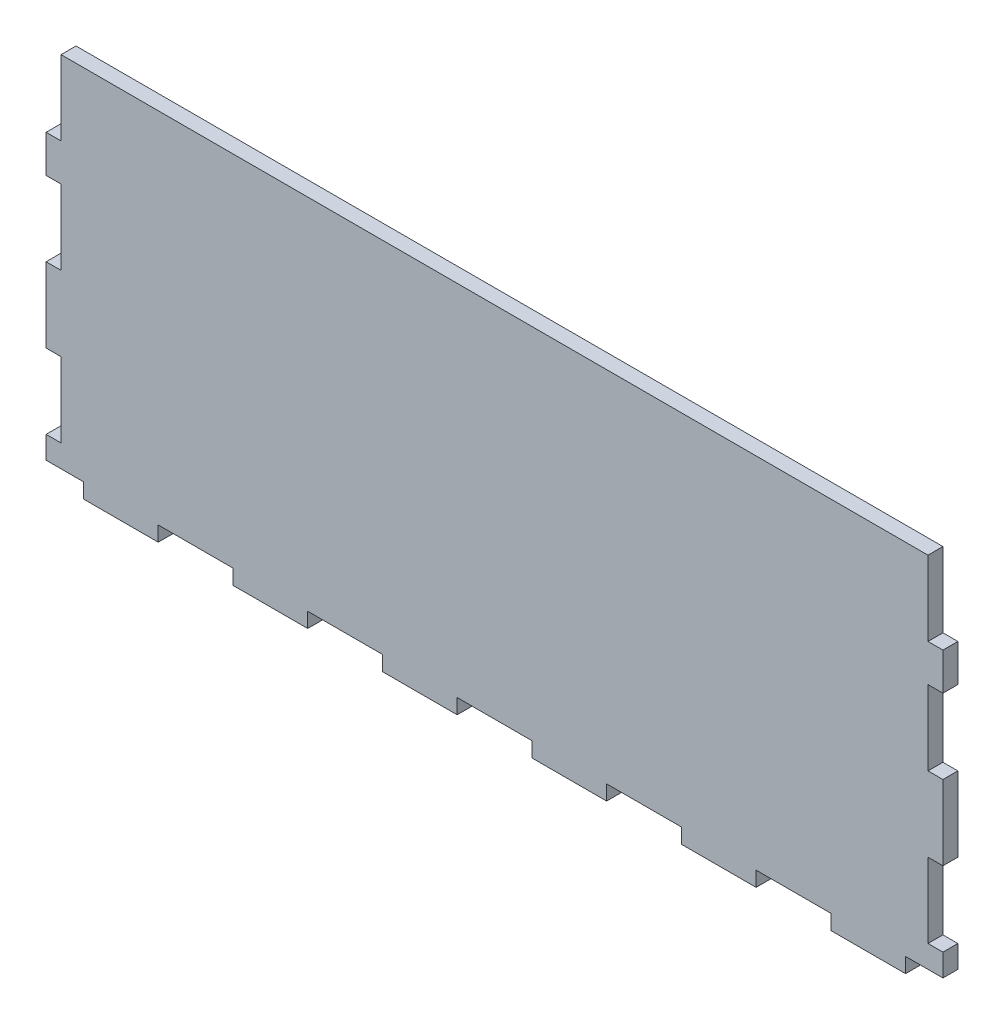
SolidWorks part; units mm, degrees
ref_plane "Front Plane" through (0, 0, 0) normal (0, 0, 1) x (1, 0, 0)
ref_plane "Top Plane" through (0, 0, 0) normal (0, 1, 0) x (1, 0, 0)
ref_plane "Right Plane" through (0, 0, 0) normal (1, 0, 0) x (0, 0, -1)
sketch "Sketch1" plane through (0, 0, 0) normal (0, 0, 1) x (1, 0, 0)
  line L0 (0, 0) -> (0, -127) construction
  line L1 (152.4, 0) -> (-152.4, 0)
  line L2 (12.7, -127) -> (-12.7, -127)
  line L3 (-12.7, -127) -> (-12.7, -121.92)
  line L4 (-12.7, -121.92) -> (-38.1, -121.92)
  line L5 (-38.1, -121.92) -> (-38.1, -127)
  line L6 (-38.1, -127) -> (-63.5, -127)
  line L7 (-63.5, -127) -> (-63.5, -121.92)
  line L8 (-63.5, -121.92) -> (-88.9, -121.92)
  line L9 (-88.9, -121.92) -> (-88.9, -127)
  line L10 (-88.9, -127) -> (-114.3, -127)
  line L11 (-152.4, -127) -> (-152.4, -114.3)
  line L12 (-114.3, -127) -> (-114.3, -121.92)
  line L13 (-114.3, -121.92) -> (-139.7, -121.92)
  line L14 (-139.7, -121.92) -> (-139.7, -127)
  line L15 (-139.7, -127) -> (-152.4, -127)
  line L16 (-152.4, -114.3) -> (-147.32, -114.3)
  line L17 (-147.32, -114.3) -> (-147.32, -88.9)
  line L18 (-147.32, -88.9) -> (-152.4, -88.9)
  line L19 (-152.4, -63.5) -> (-147.32, -63.5)
  line L20 (-147.32, -63.5) -> (-147.32, -38.1)
  line L21 (-147.32, -38.1) -> (-152.4, -38.1)
  line L22 (-152.4, -25.4) -> (-147.32, -25.4)
  line L23 (-147.32, -25.4) -> (-147.32, 0)
  line L24 (-152.4, -88.9) -> (-152.4, -63.5)
  line L25 (-152.4, -38.1) -> (-152.4, -25.4)
  line L26 (152.4, -38.1) -> (152.4, -25.4)
  line L27 (152.4, -88.9) -> (152.4, -63.5)
  line L28 (147.32, -25.4) -> (147.32, 0)
  line L29 (152.4, -25.4) -> (147.32, -25.4)
  line L30 (147.32, -38.1) -> (152.4, -38.1)
  line L31 (147.32, -63.5) -> (147.32, -38.1)
  line L32 (152.4, -63.5) -> (147.32, -63.5)
  line L33 (147.32, -88.9) -> (152.4, -88.9)
  line L34 (147.32, -114.3) -> (147.32, -88.9)
  line L35 (152.4, -114.3) -> (147.32, -114.3)
  line L36 (139.7, -127) -> (152.4, -127)
  line L37 (139.7, -121.92) -> (139.7, -127)
  line L38 (114.3, -121.92) -> (139.7, -121.92)
  line L39 (114.3, -127) -> (114.3, -121.92)
  line L40 (152.4, -127) -> (152.4, -114.3)
  line L41 (88.9, -127) -> (114.3, -127)
  line L42 (88.9, -121.92) -> (88.9, -127)
  line L43 (63.5, -121.92) -> (88.9, -121.92)
  line L44 (63.5, -127) -> (63.5, -121.92)
  line L45 (38.1, -127) -> (63.5, -127)
  line L46 (38.1, -121.92) -> (38.1, -127)
  line L47 (12.7, -121.92) -> (38.1, -121.92)
  line L48 (12.7, -127) -> (12.7, -121.92)
  line L49 (-147.32, 0) -> (147.32, 0)
  line L50 (-152.4, 0) -> (-152.4, -127)
  line L51 (-152.4, -127) -> (152.4, -127)
  line L52 (152.4, -127) -> (152.4, 0)
  line L53 (-147.32, 0) -> (-147.32, -114.3)
  line L54 (-139.7, -121.92) -> (139.7, -121.92)
  line L55 (147.32, 0) -> (147.32, -114.3)
  line L56 (-139.7, -121.92) -> (-152.4, -121.92)
  line L57 (139.7, -121.92) -> (152.4, -121.92)
  line L58 (-147.32, -114.3) -> (-147.32, -121.92)
  line L59 (147.32, -114.3) -> (147.32, -121.92)
  dimension "D1" = 152.4
  dimension "D2" = 127
  dimension "D3" = 12.7
  dimension "D4" = 25.4
  dimension "D5" = 5.08
  dimension "D6" = 12.7
  dimension "D7" = 25.4
extrude "Boss-Extrude1" add sketch "Sketch1" along normal mid plane 5.08 contours L53 L19 L24 L18 | L53 L22 L25 L21 | L58 L16 L50 L56 | L0 L49 L23 L53 L20 L17 L58 L56 L13 L54 L8 L4 | L14 L51 L12 L13 | L9 L51 L7 L8 | L5 L51 L3 L4 | L48 L51 L46 L47 | L1 L0 L54 L47 L43 L38 L57 L59 L34 L55 L31 L28 | L44 L51 L42 L43 | L39 L51 L37 L38 | L35 L59 L57 L52 | L32 L55 L33 L27 | L29 L55 L30 L26 region at (73.66, -60.96, 0) region at (-73.66, -60.96, 0) region at (-25.4, -124.46, 0) region at (25.4, -124.46, 0) region at (149.86, -31.75, 0) region at (-149.86, -31.75, 0) region at (-76.2, -124.46, 0) region at (76.2, -124.46, 0) region at (149.86, -76.2, 0) region at (-149.86, -76.2, 0) region at (-127, -124.46, 0) region at (127, -124.46, 0) region at (149.86, -118.11, 0) region at (-149.86, -118.11, 0)
